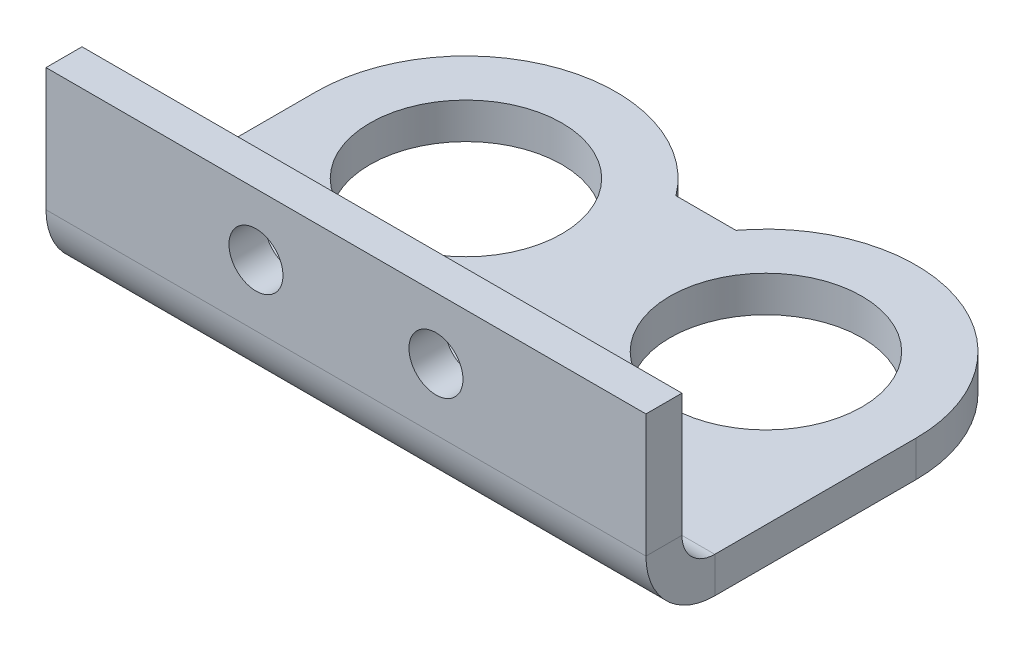
SolidWorks part; units mm, degrees
note: The reader was unsure of these and kept them because the rebuilt part matched: flange length of "边线-法兰1".
ref_plane "前视基准面" through (0, 0, 0) normal (0, 0, 1) x (1, 0, 0)
ref_plane "上视基准面" through (0, 0, 0) normal (0, 1, 0) x (1, 0, 0)
ref_plane "右视基准面" through (0, 0, 0) normal (1, 0, 0) x (0, 0, -1)
sketch "草图1" plane through (0, 0, 0) normal (0, 1, 0) x (1, 0, 0)
  line L0 (0, 0) -> (0, 46.1548) construction
  line L1 (54.8972, 0) -> (-54.8972, 0) construction
  line L2 (-25, 22.5) -> (-25, 0)
  line L3 (-2.5, 30) -> (2.5, 30)
  line L4 (-25, 0) -> (25, 0)
  line L5 (25, 22.5) -> (25, 0)
  circle A0 centre (-12.5, 22.5) radius 8
  arc A1 (-2.5, 30) -> (-25, 22.5) centre (-12.5, 22.5) ccw
  arc A2 (2.5, 30) -> (25, 22.5) centre (12.5, 22.5) cw
  circle A3 centre (12.5, 22.5) radius 8
  point P16 (0, 30)
  dimension "D1" = 16
  dimension "D2" = 25
  dimension "D4" = 22.5
  dimension "D3" = 50
  dimension "D5" = 30
base flange "基体-法兰1" sketch "草图1" thickness 3 reverse thickness direction no parameters "D1"=2.7366
edge flange "边线-法兰1" sketch "草图8" flange angle 90 flange length 16 flange position material inside bend radius 2.7366 thickness 3 relief rectangular parameters "D6"=10
sketch "草图8" plane through (0, 0, 0) normal (0, 0, -1) x (-1, 0, 0)
  line L1 (25, 0) -> (-25, 0) construction
  line L2 (-25, 0) -> (-25, 13)
  line L3 (-25, 13) -> (25, 13)
  line L4 (25, 13) -> (25, 0)
  line L5 (25, 0) -> (-25, 0)
bend "边线折弯1" bend radius 2.7366 bend angle 90 parameters "D5"=1
sketch "草图9" plane through (0, 0, 0) normal (0, 0, 1) x (1, 0, 0)
  line L0 (0, 0) -> (0, 13) construction
  line L1 (-25, 13) -> (25, 13) construction
  line L3 (25, 7.8683) -> (0, 7.8683) construction
  line L4 (25, 13) -> (25, 2.7366) construction
  circle A0 centre (7.5, 7.8683) radius 2.25
  circle A1 centre (-7.5, 7.8683) radius 2.25
  point P9 (0, 0)
  dimension "D2" = 4.5
  dimension "D1" = 15
extrude "切除-拉伸1" cut sketch "草图9" against normal blind 10 normal cut yes
sketch "折弯-线1" plane through (0, 0, 0) normal (0, 1, 0) x (1, 0, 0)
sketch "边界框1" plane through (0, 0, 0) normal (0, 1, 0) x (1, 0, 0)
sheet metal parameters "钣金6" thickness 3 parameters "D1"=2.7366
flat pattern "平板型式6" [suppressed]
sketch "折弯-线2" plane through (0, 0, 0) normal (0, 1, 0) x (1, 0, 0)
sketch "边界框2" [suppressed] plane through (0, 0, 0) normal (0, 1, 0) x (1, 0, 0)
sheet metal parameters "钣金7" thickness 3 parameters "D1"=2.7366
flat pattern "平板型式6" [suppressed]
sketch "折弯-线2" plane through (0, 0, 0) normal (0, 1, 0) x (1, 0, 0)
sketch "边界框2" [suppressed] plane through (0, 0, 0) normal (0, 1, 0) x (1, 0, 0)
bend of the flat pattern "展开-<边线折弯1>1"
sheet metal parameters "钣金8" thickness 3 parameters "D1"=2.7366
flat pattern "平板型式6" [suppressed]
sketch "折弯-线2" plane through (0, 0, 0) normal (0, 1, 0) x (1, 0, 0)
sketch "边界框2" [suppressed] plane through (0, 0, 0) normal (0, 1, 0) x (1, 0, 0)
bend of the flat pattern "展开-<边线折弯1>1"
